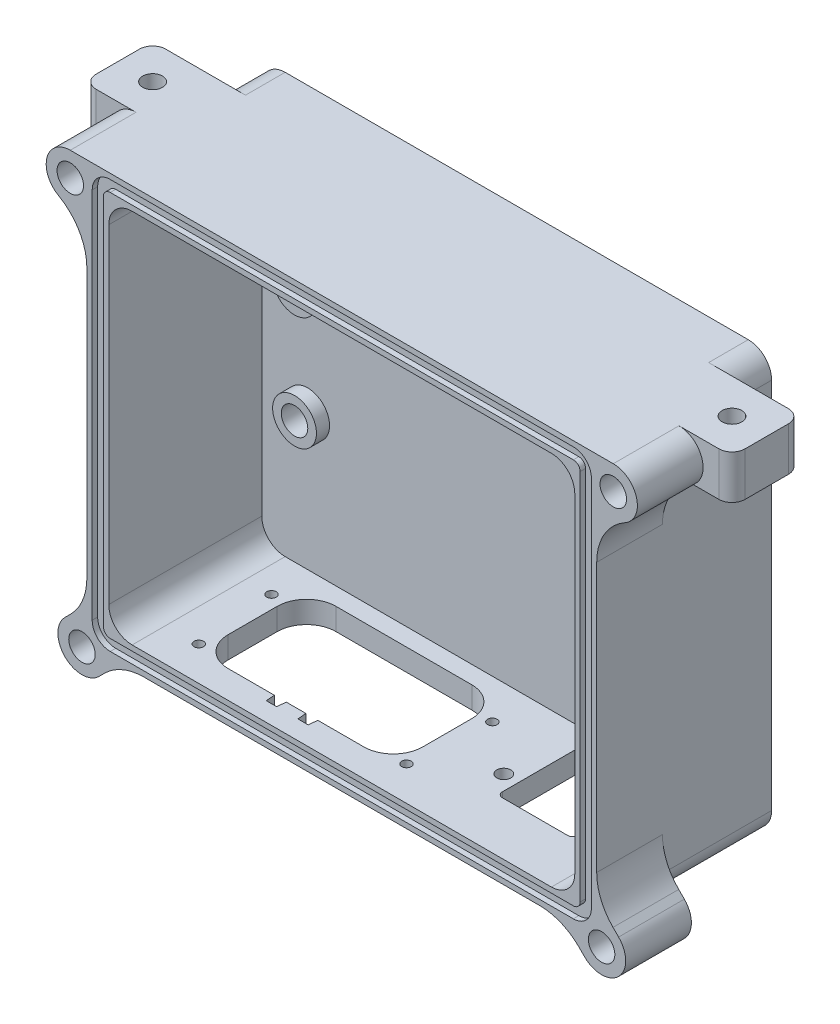
SolidWorks part; units mm, degrees
material "ABS"
ref_plane "X-Y Datum" through (0, 0, 0) normal (0, 0, 1) x (1, 0, 0)
ref_plane "X-Z Datum" through (0, 0, 0) normal (0, 1, 0) x (1, 0, 0)
ref_plane "Y-Z Datum" through (0, 0, 0) normal (1, 0, 0) x (0, 0, -1)
sketch "Sketch1" plane through (0, 0, 0) normal (0, 0, 1) x (1, 0, 0)
  line L1 (-53.1813, 42.8625) -> (53.1812, 42.8625)
  line L2 (-53.1813, 42.8625) -> (-53.1812, -42.8625)
  line L3 (-53.1812, -42.8625) -> (53.1813, -42.8625)
  line L4 (53.1812, 42.8625) -> (53.1813, -42.8625)
  line L5 (-53.1813, 42.8625) -> (53.1813, -42.8625) construction
  line L6 (-53.1812, -42.8625) -> (53.1812, 42.8625) construction
  point P0 (0, 0)
  dimension "D1" = 106.3625
  dimension "D2" = 85.725
extrude "Boss-Extrude1" add sketch "Sketch1" along normal blind 34.925
shell "Shell1" thickness 5 removed face at (0, 0, 34.925) outward yes
fillet "Fillet1" radius 5.334 8 edges at (-58.1812, -47.8625, 14.9625) (58.1813, -47.8625, 14.9625) (53.1812, 42.8625, 17.4625) (58.1812, 47.8625, 14.9625) (-58.1813, 47.8625, 14.9625) (-53.1813, 42.8625, 17.4625) (53.1813, -42.8625, 17.4625) (-53.1812, -42.8625, 17.4625)
sketch "Sketch2" plane through (0, 0, 34.925) normal (0, 0, 1) x (1, 0, 0)
  line L20 (-52.8472, -46.6452) -> (52.8472, -46.6452)
  line L21 (56.9639, -42.5285) -> (56.9639, 42.5285)
  line L22 (52.8472, 46.6452) -> (-52.8473, 46.6452)
  line L23 (-56.9639, 42.5285) -> (-56.9639, -42.5285)
  line L24 (-52.8472, -45.3625) -> (52.8473, -45.3625)
  line L25 (55.6812, -42.5285) -> (55.6812, 42.5285)
  line L26 (52.8472, 45.3625) -> (-52.8473, 45.3625)
  line L27 (-55.6812, 42.5285) -> (-55.6812, -42.5285)
  line L28 (-52.8472, -45.3625) -> (52.8473, -45.3625) construction
  line L29 (55.6812, -42.5285) -> (55.6812, 42.5285) construction
  line L30 (52.8472, 45.3625) -> (-52.8473, 45.3625) construction
  line L31 (-55.6812, 42.5285) -> (-55.6812, -42.5285) construction
  line L32 (-54.3986, 42.5285) -> (-54.3986, -42.5285)
  line L33 (-52.8472, -44.0798) -> (52.8472, -44.0798)
  line L34 (54.3986, -42.5285) -> (54.3986, 42.5285)
  line L35 (52.8472, 44.0798) -> (-52.8473, 44.0798)
  arc A16 (52.8472, -46.6452) -> (56.9639, -42.5285) centre (52.8473, -42.5285) ccw
  arc A17 (56.9639, 42.5285) -> (52.8472, 46.6452) centre (52.8472, 42.5285) ccw
  arc A18 (-52.8473, 46.6452) -> (-56.9639, 42.5285) centre (-52.8473, 42.5285) ccw
  arc A19 (-56.9639, -42.5285) -> (-52.8472, -46.6452) centre (-52.8472, -42.5285) ccw
  arc A20 (-55.6812, -42.5285) -> (-52.8472, -45.3625) centre (-52.8472, -42.5285) ccw
  arc A21 (52.8473, -45.3625) -> (55.6812, -42.5285) centre (52.8473, -42.5285) ccw
  arc A22 (55.6812, 42.5285) -> (52.8472, 45.3625) centre (52.8472, 42.5285) ccw
  arc A23 (-52.8473, 45.3625) -> (-55.6812, 42.5285) centre (-52.8473, 42.5285) ccw
  arc A24 (-55.6812, -42.5285) -> (-52.8472, -45.3625) centre (-52.8472, -42.5285) ccw construction
  arc A25 (52.8473, -45.3625) -> (55.6812, -42.5285) centre (52.8473, -42.5285) ccw construction
  arc A26 (55.6812, 42.5285) -> (52.8472, 45.3625) centre (52.8472, 42.5285) ccw construction
  arc A27 (-52.8473, 45.3625) -> (-55.6812, 42.5285) centre (-52.8473, 42.5285) ccw construction
  arc A28 (-52.8473, 44.0798) -> (-54.3986, 42.5285) centre (-52.8473, 42.5285) ccw
  arc A29 (-54.3986, -42.5285) -> (-52.8472, -44.0798) centre (-52.8472, -42.5285) ccw
  arc A30 (52.8472, -44.0798) -> (54.3986, -42.5285) centre (52.8473, -42.5285) ccw
  arc A31 (54.3986, 42.5285) -> (52.8472, 44.0798) centre (52.8472, 42.5285) ccw
  dimension "D4" = 2.5654
  dimension "D1" = 2.5
  dimension "D2" = 1.2827
  dimension "D3" = 1.2827
extrude "Cut-Extrude1" cut sketch "Sketch2" against normal blind 1.2446
sketch "Sketch4" plane through (0, 0, 34.925) normal (0, 0, 1) x (1, 0, 0)
  line L0 (56.9639, -42.5285) -> (56.9639, 42.5285) construction
  line L1 (52.8472, 47.8625) -> (-52.8473, 47.8625) construction
  line L2 (61.9639, 47.8625) -> (52.8472, 47.8625)
  line L3 (61.9639, 36.8625) -> (58.1813, 36.8625)
  line L4 (58.1813, -42.5285) -> (58.1812, 42.5285) construction
  line L6 (47.8473, -37.5285) -> (59.2937, -48.975)
  line L7 (55.4046, -52.8641) -> (50.4031, -47.8625)
  line L8 (-52.8472, -47.8625) -> (52.8473, -47.8625) construction
  line L9 (63.1828, -45.0859) -> (58.1813, -40.0843)
  line L10 (-52.8472, -47.8625) -> (52.8473, -47.8625)
  line L11 (58.1813, -42.5285) -> (58.1812, 42.5285)
  circle A0 centre (61.9639, 42.3625) radius 3.025
  circle A1 centre (61.9639, 42.3625) radius 5.5
  arc A2 (47.8473, -42.8625) -> (53.1813, -37.5285) centre (47.8473, -37.5285) ccw construction
  circle A3 centre (59.2937, -48.975) radius 3.025
  circle A4 centre (59.2937, -48.975) radius 5.5
  arc A5 (52.8472, -46.6452) -> (56.9639, -42.5285) centre (52.8473, -42.5285) ccw construction
  arc A6 (52.8473, -47.8625) -> (58.1813, -42.5285) centre (52.8473, -42.5285) ccw construction
  arc A7 (58.1812, 42.5285) -> (52.8472, 47.8625) centre (52.8472, 42.5285) ccw construction
  arc A8 (52.8473, -47.8625) -> (58.1813, -42.5285) centre (52.8473, -42.5285) ccw
  arc A9 (58.1812, 42.5285) -> (52.8472, 47.8625) centre (52.8472, 42.5285) ccw
  point P14 (51.619, -41.3002)
  point P23 (55.7582, -45.4394)
  dimension "D1" = 6.05
  dimension "D2" = 11
  dimension "D3" = 5
  dimension "D4" = 5
extrude "Boss-Extrude2" add sketch "Sketch4" against normal blind 15 separate body contours A9 L11 A1 A0 | A9 A1 L2 | A0 | A8 A4 L9 L11 | A8 L10 L7 A4 | A8 A4 A3 | A3 | A1 L11 L3 region at (57.3854, 47.158, 34.925) region at (59.5123, -42.505, 34.925) region at (65.7474, 46.146, 34.925) region at (59.099, 37.3017, 34.925) region at (60.4186, -46.2593, 34.925) region at (64.2313, -46.9298, 34.925) region at (52.8237, -49.1935, 34.925) region at (61.9639, 42.3625, 34.925)
sketch "Sketch5" plane through (0, 0, 34.925) normal (0, 0, 1) x (1, 0, 0)
  line L0 (61.9639, 36.8625) -> (58.1813, 36.8625) construction
  line L1 (61.9639, 47.8625) -> (52.8472, 47.8625) construction
  line L2 (58.1813, -42.5285) -> (58.1812, 42.5285) construction
  line L3 (-52.8472, -47.8625) -> (52.8473, -47.8625) construction
  line L4 (63.1828, -45.0859) -> (58.1813, -40.0843) construction
  line L5 (55.4046, -52.8641) -> (50.4031, -47.8625) construction
  line L6 (47.8473, -37.5285) -> (59.2937, -48.975) construction
  line L7 (61.9639, 36.8625) -> (58.1813, 36.8625)
  line L8 (61.9639, 47.8625) -> (52.8472, 47.8625)
  line L9 (58.1813, -42.5285) -> (58.1812, 42.5285)
  line L10 (-52.8472, -47.8625) -> (52.8473, -47.8625)
  line L11 (63.1828, -45.0859) -> (58.1813, -40.0843)
  line L12 (55.4046, -52.8641) -> (50.4031, -47.8625)
  line L13 (47.8473, -37.5285) -> (59.2937, -48.975)
  arc A0 (58.1812, 42.5285) -> (52.8472, 47.8625) centre (52.8472, 42.5285) ccw construction
  circle A1 centre (59.2937, -48.975) radius 3.025
  circle A2 centre (59.2937, -48.975) radius 3.025
  circle A3 centre (61.9639, 42.3625) radius 5.5
  circle A4 centre (61.9639, 42.3625) radius 5.5
  circle A5 centre (61.9639, 42.3625) radius 3.025
  circle A6 centre (61.9639, 42.3625) radius 3.025
  circle A7 centre (59.2937, -48.975) radius 5.5
  circle A8 centre (59.2937, -48.975) radius 5.5
  arc A9 (52.8473, -47.8625) -> (58.1813, -42.5285) centre (52.8473, -42.5285) ccw construction
  arc A10 (58.1812, 42.5285) -> (52.8472, 47.8625) centre (52.8472, 42.5285) ccw
  arc A11 (52.8473, -47.8625) -> (58.1813, -42.5285) centre (52.8473, -42.5285) ccw
  dimension "D1" = 0
  dimension "D2" = 0
  dimension "D3" = 0
  dimension "D4" = 0
extrude "Cut-Extrude4" cut sketch "Sketch5" against normal blind 8 contours A6 | A2 region at (60.4186, -46.2593, 34.925) region at (61.9639, 42.3625, 34.925)
mirror "Mirror3" about plane through (0, 0, 0) normal (1, 0, 0) of bodies 107 106
combine bodies "Combine3" operation type add bodies to combine 102 107 106 109 110
fillet "Fillet2" radius 12.7 6 edges at (-58.1813, 36.8625, 27.425) (-50.4031, -47.8625, 27.425) (-58.1813, -40.0843, 27.425) (50.4031, -47.8625, 27.425) (58.1813, -40.0843, 27.425) (58.1813, 36.8625, 27.425)
sketch "Sketch8" plane through (0, 47.8625, 0) normal (0, 1, 0) x (1, 0, 0)
  line L0 (0, 5) -> (0, -34.925)
  line L2 (52.8472, 5) -> (-52.8473, 5) construction
  line L3 (61.9639, -34.925) -> (-61.9639, -34.925) construction
  line L4 (-61.9639, -19.925) -> (-52.8473, -19.925) construction
  line L5 (-74.0562, -19.925) -> (74.0562, -19.925)
  line L6 (-74.0562, -19.925) -> (-74.0562, -4.05)
  line L7 (-74.0562, -4.05) -> (74.0562, -4.05)
  line L8 (74.0562, -19.925) -> (74.0562, -4.05)
  line L9 (-74.0562, -19.925) -> (74.0562, -4.05) construction
  line L10 (-74.0562, -4.05) -> (74.0562, -19.925) construction
  line L11 (-58.1812, -19.925) -> (-58.1813, 5) construction
  line L12 (-58.1812, -19.925) -> (-58.1812, -4.05)
  line L13 (-74.0562, -19.925) -> (-58.1812, -4.05)
  line L14 (52.8472, -19.925) -> (52.8472, 5) construction
  line L15 (58.1812, 5) -> (58.1812, -19.925) construction
  line L16 (52.8472, -19.925) -> (52.8472, 5)
  line L17 (58.1812, 5) -> (58.1812, -19.925)
  line L18 (58.1812, -19.925) -> (74.0562, -4.05)
  circle A0 centre (-66.1187, -11.9875) radius 2
  circle A1 centre (66.1187, -11.9875) radius 2
  point P5 (0, -11.9875)
  line M8 (61.9639, -19.925) -> (52.8472, -19.925)
  dimension "D3" = 4
  dimension "D1" = 15.875
  dimension "D2" = 15.875
extrude "Boss-Extrude4" add sketch "Sketch8" against normal blind 10 contours A0 L13 L5 L12 | A0 L13 L7 L6 | L13 A0 | L13 A0 | A1 L18 L7 L17 | L18 A1 | L18 A1 | A1 L18 L5 L8 M8 region at (-68.8719, 47.8625, 9.2343) region at (-63.3656, 47.8625, 14.7407) region at (-65.5185, 47.8625, 12.5877) region at (-66.719, 47.8625, 11.3873) region at (63.3656, 47.8625, 9.2343) region at (68.8719, 47.8625, 14.7407) region at (65.5185, 47.8625, 11.3873) region at (66.719, 47.8625, 12.5877)
sketch "Sketch9" plane through (0, 47.8625, 0) normal (0, 1, 0) x (1, 0, 0)
  line L0 (-58.1812, -19.925) -> (-58.1812, -4.05) construction
  line L1 (-74.0562, -19.925) -> (-58.1812, -4.05) construction
  line L2 (0, 5) -> (0, -34.925) construction
  line L3 (-74.0562, -19.925) -> (74.0562, -19.925) construction
  line L4 (74.0562, -19.925) -> (74.0562, -4.05) construction
  line L5 (-74.0562, -4.05) -> (74.0562, -4.05) construction
  line L6 (-74.0562, -19.925) -> (-74.0562, -4.05) construction
  line L7 (-58.1812, -19.925) -> (-58.1812, -4.05)
  line L8 (-74.0562, -19.925) -> (-58.1812, -4.05)
  line L9 (0, 5) -> (0, -34.925)
  line L10 (-74.0562, -19.925) -> (74.0562, -19.925)
  line L11 (74.0562, -19.925) -> (74.0562, -4.05)
  line L12 (-74.0562, -4.05) -> (74.0562, -4.05)
  line L13 (-74.0562, -19.925) -> (-74.0562, -4.05)
  line L14 (-52.8473, 5) -> (-52.8473, -19.925) construction
  line L15 (-52.8473, 5) -> (-52.8473, -19.925)
  line L16 (52.8472, -19.925) -> (52.8472, 5) construction
  line L17 (52.8472, -19.925) -> (52.8472, 5)
  circle A0 centre (-66.1187, -11.9875) radius 2 construction
  circle A1 centre (-66.1187, -11.9875) radius 2
  line M6 (-52.8473, 5) -> (-52.8473, -19.925)
  line M7 (-52.8473, -19.925) -> (-58.1812, -19.925)
  line M8 (-58.1812, -19.925) -> (-58.1812, -4.05)
extrude "Boss-Extrude5" add sketch "Sketch9" against normal up to surface contours L12 M8 M7 M6 region at (-55.5143, 47.8625, 11.9875) up to face at (-56.4895, 45.104, 6.78)
fillet "Fillet3" radius 3 4 edges at (-74.0562, 42.8625, 19.925) (-74.0562, 42.8625, 4.05) (74.0562, 42.8625, 19.925) (74.0562, 42.8625, 4.05)
sketch "Sketch12" plane through (0, 47.8625, 0) normal (0, 1, 0) x (1, 0, 0)
  line L0 (52.8472, -19.925) -> (52.8472, 5) construction
  line L1 (-52.8473, 5) -> (-52.8473, -19.925) construction
  line L2 (-58.1812, -19.925) -> (-58.1812, -4.05) construction
  line L3 (-74.0562, -19.925) -> (-58.1812, -4.05) construction
  line L4 (-74.0562, -19.925) -> (74.0562, -19.925) construction
  line L5 (74.0562, -19.925) -> (74.0562, -4.05) construction
  line L6 (-74.0562, -4.05) -> (74.0562, -4.05) construction
  line L7 (-74.0562, -19.925) -> (-74.0562, -4.05) construction
  line L8 (0, 5) -> (0, -34.925) construction
  line L9 (52.8472, -19.925) -> (52.8472, 5)
  line L10 (-52.8473, 5) -> (-52.8473, -19.925)
  line L11 (-58.1812, -19.925) -> (-58.1812, -4.05)
  line L12 (-74.0562, -19.925) -> (-58.1812, -4.05)
  line L13 (-74.0562, -19.925) -> (74.0562, -19.925)
  line L14 (74.0562, -19.925) -> (74.0562, -4.05)
  line L15 (-74.0562, -4.05) -> (74.0562, -4.05)
  line L16 (-74.0562, -19.925) -> (-74.0562, -4.05)
  line L17 (0, 5) -> (0, -34.925)
  circle A1 centre (-66.1187, -11.9875) radius 2
  circle A2 centre (-66.1187, -11.9875) radius 2
  line M12 (58.1812, -4.05) -> (58.1812, -19.925)
  line M13 (58.1812, -19.925) -> (52.8472, -19.925)
  line M14 (52.8472, -19.925) -> (52.8472, 5)
  dimension "D1" = 0
extrude "Boss-Extrude6" add sketch "Sketch12" against normal up to surface (5.334 mm away) contours L15 M14 M13 M12 region at (55.5142, 47.8625, 11.9875) up to face at (56.4895, 45.104, 6.78)
hole_wizard "M4 Clearance Hole1" positions "Sketch10" profile "Sketch11" hole size "M4" standard "ANSI Metric" end condition through all
sketch "Sketch10" plane through (0, 37.8625, 0) normal (0, -1, 0) x (-1, 0, 0)
  point P0 (66.1187, -11.9875)
  point P4 (-66.1187, -11.9875)
sketch "Sketch11" plane through (-66.1187, 37.8625, 11.9875) normal (1, 0, 0) x (0, 0, -1)
  line L0 (0, 0) -> (0, 10)
  line L1 (0, 10) -> (2.25, 10)
  line L2 (2.25, 10) -> (2.25, 0)
  line L5 (2.25, 0) -> (0, 0)
  line L11 (0, -6.35) -> (0, 107.95) construction
  dimension "Thru Hole Dia." = 4.5
  dimension "Thru Hole Depth" = 10
sketch "Sketch13" plane through (0, -47.8625, 0) normal (0, -1, 0) x (1, 0, 0)
  line L12 (-12.2307, 28.1302) -> (-12.4056, 30.1302) construction
  line L13 (-13.8557, 30.1302) -> (-12.4056, 30.1302) construction
  line L14 (-14.0307, 28.1302) -> (-13.8557, 30.1302) construction
  line L15 (-19.4307, 28.1302) -> (-14.0307, 28.1302) construction
  line L16 (-19.4307, 28.1302) -> (-19.6056, 30.1302) construction
  line L17 (-21.0557, 30.1302) -> (-19.6056, 30.1302) construction
  line L18 (-21.2307, 28.1302) -> (-21.0557, 30.1302) construction
  line L19 (-12.2307, 28.1302) -> (-1.2307, 28.1302) construction
  line L36 (4.9693, 21.9302) -> (4.9693, 10.7302) construction
  line L37 (-1.2307, 4.5302) -> (-32.2307, 4.5302) construction
  line L38 (-38.4307, 10.7302) -> (-38.4307, 21.9302) construction
  line L39 (-32.2307, 28.1302) -> (-21.2307, 28.1302) construction
  line L40 (-11.7725, 28.6302) -> (-11.9475, 30.6302)
  line L41 (-14.3138, 30.6302) -> (-11.9475, 30.6302)
  line L42 (-14.4888, 28.6302) -> (-14.3138, 30.6302)
  line L43 (-18.9725, 28.6302) -> (-14.4888, 28.6302)
  line L44 (-18.9725, 28.6302) -> (-19.1475, 30.6302)
  line L45 (-21.5138, 30.6302) -> (-19.1475, 30.6302)
  line L46 (-21.6888, 28.6302) -> (-21.5138, 30.6302)
  line L47 (-32.2307, 28.6302) -> (-21.6888, 28.6302)
  line L48 (-38.9307, 10.7302) -> (-38.9307, 21.9302)
  line L49 (-1.2307, 4.0302) -> (-32.2307, 4.0302)
  line L50 (5.4693, 21.9302) -> (5.4693, 10.7302)
  line L51 (-11.7725, 28.6302) -> (-1.2307, 28.6302)
  line L56 (40.1813, 21.725) -> (40.1813, 5.275) construction
  line L57 (39.5313, 4.625) -> (24.5813, 4.625) construction
  line L58 (23.9313, 5.275) -> (23.9313, 21.725) construction
  line L59 (24.5813, 22.375) -> (39.5313, 22.375) construction
  line L60 (45.1426, 34.925) -> (-45.1426, 34.925)
  line L61 (-45.1426, 34.925) -> (-45.1426, 19.925)
  line L62 (-45.1426, 19.925) -> (-52.8473, 19.925)
  line L63 (-52.8473, 19.925) -> (-52.8472, -5)
  line L64 (-52.8472, -5) -> (52.8473, -5)
  line L65 (52.8473, -5) -> (52.8473, 19.925)
  line L66 (52.8473, 19.925) -> (45.1426, 19.925)
  line L67 (45.1426, 19.925) -> (45.1426, 34.925)
  line L74 (52.8473, 19.925) -> (45.1426, 19.925)
  line L76 (40.6813, 21.725) -> (40.6813, 5.275)
  line L77 (39.5313, 4.125) -> (24.5813, 4.125)
  line L78 (23.4313, 5.275) -> (23.4313, 21.725)
  line L79 (24.5813, 22.875) -> (39.5313, 22.875)
  arc A4 (4.9693, 21.9302) -> (-1.2307, 28.1302) centre (-1.2307, 21.9302) ccw construction
  arc A5 (-1.2307, 4.5302) -> (4.9693, 10.7302) centre (-1.2307, 10.7302) ccw construction
  arc A6 (-38.4307, 10.7302) -> (-32.2307, 4.5302) centre (-32.2307, 10.7302) ccw construction
  arc A7 (-32.2307, 28.1302) -> (-38.4307, 21.9302) centre (-32.2307, 21.9302) ccw construction
  arc A8 (-32.2307, 28.6302) -> (-38.9307, 21.9302) centre (-32.2307, 21.9302) ccw
  arc A9 (-38.9307, 10.7302) -> (-32.2307, 4.0302) centre (-32.2307, 10.7302) ccw
  arc A10 (-1.2307, 4.0302) -> (5.4693, 10.7302) centre (-1.2307, 10.7302) ccw
  arc A11 (5.4693, 21.9302) -> (-1.2307, 28.6302) centre (-1.2307, 21.9302) ccw
  arc A16 (40.1813, 21.725) -> (39.5313, 22.375) centre (39.5313, 21.725) ccw construction
  arc A17 (39.5313, 4.625) -> (40.1813, 5.275) centre (39.5313, 5.275) ccw construction
  arc A18 (23.9313, 5.275) -> (24.5813, 4.625) centre (24.5813, 5.275) ccw construction
  arc A19 (24.5813, 22.375) -> (23.9313, 21.725) centre (24.5813, 21.725) ccw construction
  arc A20 (39.5313, 4.125) -> (40.6813, 5.275) centre (39.5313, 5.275) ccw
  arc A21 (23.4313, 5.275) -> (24.5813, 4.125) centre (24.5813, 5.275) ccw
  arc A22 (24.5813, 22.875) -> (23.4313, 21.725) centre (24.5813, 21.725) ccw
  arc A23 (40.6813, 21.725) -> (39.5313, 22.875) centre (39.5313, 21.725) ccw
  circle A34 centre (44.0563, 9) radius 1.6
  circle A35 centre (20.0563, 18) radius 1.6
  arc A36 (8.0543, 27.1302) -> (5.8843, 27.1302) centre (6.9693, 27.1302) ccw
  arc A37 (5.8843, 27.1302) -> (8.0543, 27.1302) centre (6.9693, 27.1302) ccw
  arc A38 (9.5543, 9.0302) -> (7.3843, 9.0302) centre (8.4693, 9.0302) ccw
  arc A39 (7.3843, 9.0302) -> (9.5543, 9.0302) centre (8.4693, 9.0302) ccw
  arc A40 (-40.8457, 9.0302) -> (-43.0157, 9.0302) centre (-41.9307, 9.0302) ccw
  arc A41 (-43.0157, 9.0302) -> (-40.8457, 9.0302) centre (-41.9307, 9.0302) ccw
  arc A42 (-39.3457, 27.1302) -> (-41.5157, 27.1302) centre (-40.4307, 27.1302) ccw
  arc A43 (-41.5157, 27.1302) -> (-39.3457, 27.1302) centre (-40.4307, 27.1302) ccw
  dimension "D1" = 0.5
  dimension "D2" = 0
  dimension "D3" = 0.5
extrude "Cut-Extrude6" cut sketch "Sketch13" against normal blind 5 contours L50 A11 L51 L40 L41 L42 L43 L44 L45 L46 L47 A8 L48 A9 L49 A10 | L76 A23 L79 A22 L78 A21 L77 A20 | A42 A43 | A40 A41 | A38 A39 | A36 A37 | A35 | A34 region at (-16.7307, -47.8625, 16.4571) region at (32.0563, -47.8625, 13.5) region at (44.0563, -47.8625, 9) region at (20.0563, -47.8625, 18) region at (6.9693, -47.8625, 27.1302) region at (8.4693, -47.8625, 9.0302) region at (-41.9307, -47.8625, 9.0302) region at (-40.4307, -47.8625, 27.1302)
sketch "Sketch15" plane through (0, 0, 0) normal (0, 0, 1) x (1, 0, 0)
  line L0 (-42.7107, 16.0707) -> (-42.7107, 11.8707)
  line L1 (29.0253, 16.9787) -> (29.0253, 12.7787)
  line L2 (29.0253, -10.9613) -> (29.0253, -15.1613)
  line L3 (-42.7107, -9.8373) -> (-42.7107, -14.0373)
  circle A0 centre (29.0253, 14.8787) radius 3.025
  circle A1 centre (29.0253, -13.0613) radius 3.025
  circle A2 centre (-42.7107, -11.9373) radius 3.025
  circle A3 centre (-42.7107, 13.9707) radius 3.025
  circle A4 centre (-42.7107, -11.9373) radius 5
  circle A5 centre (-42.7107, 13.9707) radius 5
  circle A6 centre (29.0253, 14.8787) radius 5
  circle A7 centre (29.0253, -13.0613) radius 5
  spline S0 degree 3 poles (29.0253, -10.9613) (24.8253, -10.9613) (24.8253, -15.1613) (29.0253, -15.1613) (33.2253, -15.1613) (33.2253, -10.9613) (29.0253, -10.9613) (24.8253, -10.9613) (24.8253, -15.1613) knots -0.5 0 0 0 0.5 0.5 0.5 1 1 1 1.5 1.5 1.5 weights 1 0.333333 0.333333 1 0.333333 0.333333 1 0.333333 0.333333 only from (29.0253, -10.9613) to (29.0253, -10.9613) construction
  spline S1 degree 3 poles (29.0253, 16.9787) (24.8253, 16.9787) (24.8253, 12.7787) (29.0253, 12.7787) (33.2253, 12.7787) (33.2253, 16.9787) (29.0253, 16.9787) (24.8253, 16.9787) (24.8253, 12.7787) knots -0.5 0 0 0 0.5 0.5 0.5 1 1 1 1.5 1.5 1.5 weights 1 0.333333 0.333333 1 0.333333 0.333333 1 0.333333 0.333333 only from (29.0253, 16.9787) to (29.0253, 16.9787) construction
  spline S2 degree 3 poles (-42.7107, 16.0707) (-46.9107, 16.0707) (-46.9107, 11.8707) (-42.7107, 11.8707) (-38.5107, 11.8707) (-38.5107, 16.0707) (-42.7107, 16.0707) (-46.9107, 16.0707) (-46.9107, 11.8707) knots -0.5 0 0 0 0.5 0.5 0.5 1 1 1 1.5 1.5 1.5 weights 1 0.333333 0.333333 1 0.333333 0.333333 1 0.333333 0.333333 only from (-42.7107, 16.0707) to (-42.7107, 16.0707) construction
  spline S3 degree 3 poles (-42.7107, -9.8373) (-46.9107, -9.8373) (-46.9107, -14.0373) (-42.7107, -14.0373) (-38.5107, -14.0373) (-38.5107, -9.8373) (-42.7107, -9.8373) (-46.9107, -9.8373) (-46.9107, -14.0373) knots -0.5 0 0 0 0.5 0.5 0.5 1 1 1 1.5 1.5 1.5 weights 1 0.333333 0.333333 1 0.333333 0.333333 1 0.333333 0.333333 only from (-42.7107, -9.8373) to (-42.7107, -9.8373) construction
  spline S4 degree 3 poles (29.0253, -10.9613) (24.8253, -10.9613) (24.8253, -15.1613) (29.0253, -15.1613) (33.2253, -15.1613) (33.2253, -10.9613) (29.0253, -10.9613) (24.8253, -10.9613) (24.8253, -15.1613) knots -0.5 0 0 0 0.5 0.5 0.5 1 1 1 1.5 1.5 1.5 weights 1 0.333333 0.333333 1 0.333333 0.333333 1 0.333333 0.333333 only from (29.0253, -10.9613) to (29.0253, -10.9613)
  spline S5 degree 3 poles (29.0253, 16.9787) (24.8253, 16.9787) (24.8253, 12.7787) (29.0253, 12.7787) (33.2253, 12.7787) (33.2253, 16.9787) (29.0253, 16.9787) (24.8253, 16.9787) (24.8253, 12.7787) knots -0.5 0 0 0 0.5 0.5 0.5 1 1 1 1.5 1.5 1.5 weights 1 0.333333 0.333333 1 0.333333 0.333333 1 0.333333 0.333333 only from (29.0253, 16.9787) to (29.0253, 16.9787)
  spline S6 degree 3 poles (-42.7107, 16.0707) (-46.9107, 16.0707) (-46.9107, 11.8707) (-42.7107, 11.8707) (-38.5107, 11.8707) (-38.5107, 16.0707) (-42.7107, 16.0707) (-46.9107, 16.0707) (-46.9107, 11.8707) knots -0.5 0 0 0 0.5 0.5 0.5 1 1 1 1.5 1.5 1.5 weights 1 0.333333 0.333333 1 0.333333 0.333333 1 0.333333 0.333333 only from (-42.7107, 16.0707) to (-42.7107, 16.0707)
  spline S7 degree 3 poles (-42.7107, -9.8373) (-46.9107, -9.8373) (-46.9107, -14.0373) (-42.7107, -14.0373) (-38.5107, -14.0373) (-38.5107, -9.8373) (-42.7107, -9.8373) (-46.9107, -9.8373) (-46.9107, -14.0373) knots -0.5 0 0 0 0.5 0.5 0.5 1 1 1 1.5 1.5 1.5 weights 1 0.333333 0.333333 1 0.333333 0.333333 1 0.333333 0.333333 only from (-42.7107, -9.8373) to (-42.7107, -9.8373)
  point P4 (-42.7107, 13.9707)
  point P9 (-42.7107, -11.9373)
  point P10 (29.0253, -13.0613)
  point P11 (29.0253, 14.8787)
  dimension "D1" = 6.05
  dimension "D2" = 10
extrude "Boss-Extrude7" add sketch "Sketch15" along normal blind 3 contours A4 A2 | A5 A3 | A6 A0 | A7 A1 region at (-47.5693, -11.9373, 0) region at (-47.5693, 13.9707, 0) region at (24.1667, 14.8787, 0) region at (24.1667, -13.0613, 0)
sketch "Sketch16" plane through (0, 0, 0) normal (0, 0, 1) x (1, 0, 0)
  circle A0 centre (29.0253, -13.0613) radius 3.025 construction
  circle A1 centre (29.0253, 14.8787) radius 3.025 construction
  circle A2 centre (-42.7107, 13.9707) radius 3.025 construction
  circle A3 centre (-42.7107, -11.9373) radius 3.025 construction
  circle A4 centre (29.0253, -13.0613) radius 3.025
  circle A5 centre (29.0253, 14.8787) radius 3.025
  circle A6 centre (-42.7107, 13.9707) radius 3.025
  circle A7 centre (-42.7107, -11.9373) radius 3.025
extrude "Cut-Extrude7" cut sketch "Sketch16" against normal blind 2.5
